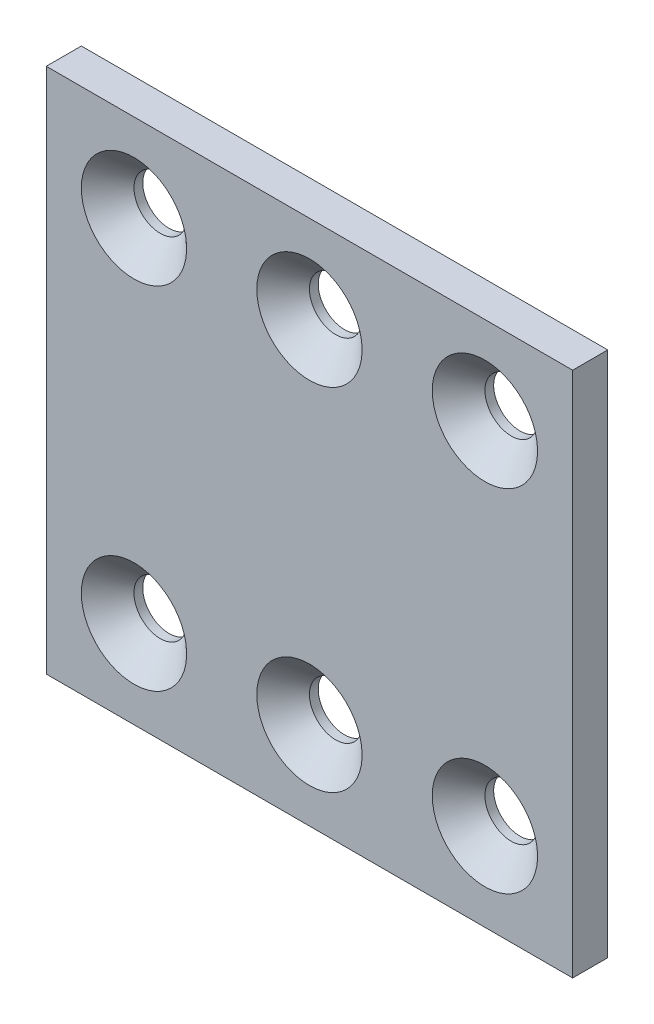
SolidWorks part; units mm, degrees
material "Aluminum 6105-T5"
ref_plane "Front Plane" through (0, 0, 0) normal (0, 0, 1) x (1, 0, 0)
ref_plane "Top Plane" through (0, 0, 0) normal (0, 1, 0) x (1, 0, 0)
ref_plane "Right Plane" through (0, 0, 0) normal (1, 0, 0) x (0, 0, -1)
sketch "Sketch1" plane through (0, 0, 0) normal (0, 0, 1) x (1, 0, 0)
  line L1 (-30, -30) -> (30, -30)
  line L2 (-30, -30) -> (-30, 30)
  line L3 (-30, 30) -> (30, 30)
  line L4 (30, -30) -> (30, 30)
  line L5 (-30, -30) -> (30, 30) construction
  line L6 (-30, 30) -> (30, -30) construction
  point P1 (0, 0)
  dimension "D2" = 60
  dimension "D3" = 60
extrude "Boss-Extrude1" add sketch "Sketch1" along normal mid plane 4
sketch "Sketch2" plane through (0, 0, 2) normal (0, 0, 1) x (1, 0, 0)
  line L0 (-20, -20) -> (0, -20) construction
  line L1 (0, -20) -> (20, -20) construction
  line L2 (20, -20) -> (20, 20) construction
  line L3 (20, 20) -> (0, 20) construction
  line L4 (0, 20) -> (-20, 20) construction
  line L5 (-20, 20) -> (-20, -20) construction
  line L6 (-20, -20) -> (20, 20) construction
  line L7 (0, 20) -> (0, 0) construction
  line L8 (0, 0) -> (0, -20) construction
  circle A0 centre (0, 20) radius 3
  circle A1 centre (0, -20) radius 3
  circle A2 centre (20, -20) radius 3
  circle A3 centre (-20, -20) radius 3
  circle A4 centre (-20, 20) radius 3
  circle A5 centre (20, 20) radius 3
  point P13 (0, 0)
  dimension "D1" = 6
  dimension "D2" = 40
  dimension "D3" = 40
extrude "Cut-Extrude1" cut sketch "Sketch2" against normal through all
chamfer "Chamfer1" distance 3 angle 45 6 edges at (23, -20, 2) (3, -20, 2) (-17, -20, 2) (23, 20, 2) (3, 20, 2) (-17, 20, 2)
fillet "Fillet1" [suppressed] radius 1
